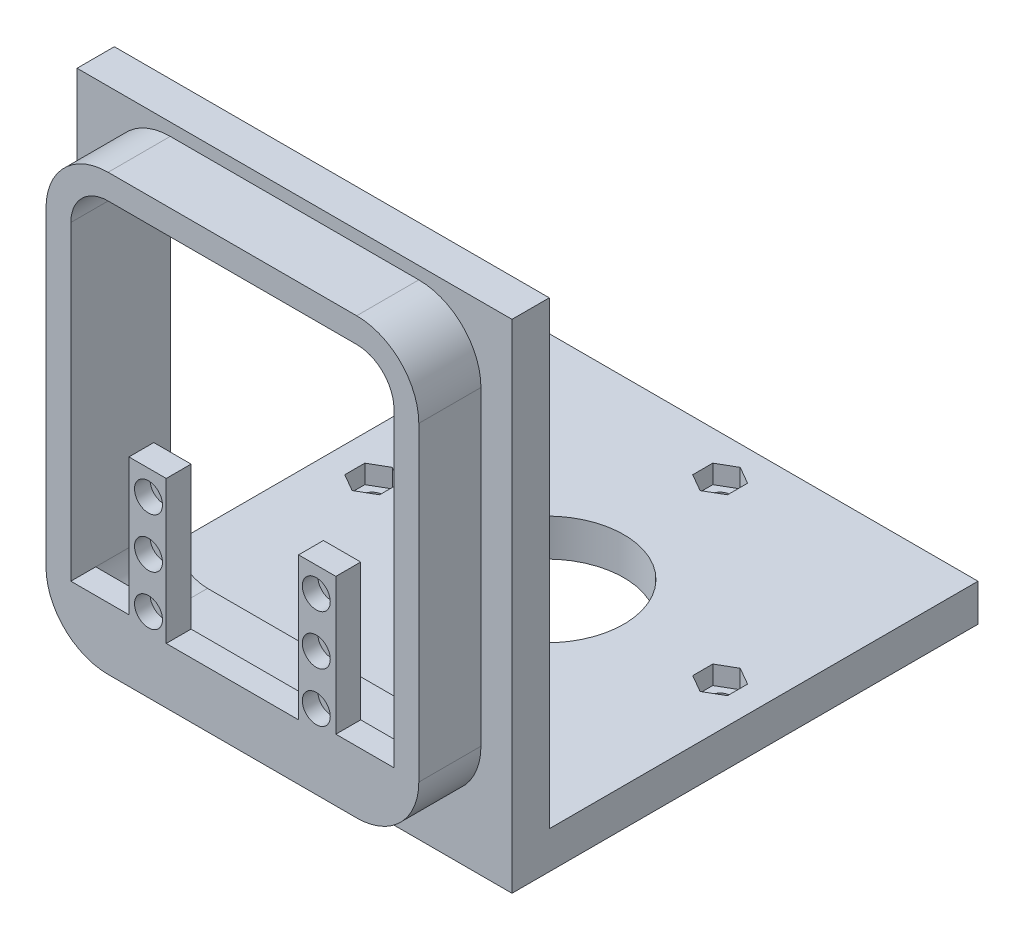
SolidWorks part; units mm, degrees
ref_plane "Front Plane" through (0, 0, 0) normal (0, 0, 1) x (1, 0, 0)
ref_plane "Top Plane" through (0, 0, 0) normal (0, 1, 0) x (1, 0, 0)
ref_plane "Right Plane" through (0, 0, 0) normal (1, 0, 0) x (0, 0, -1)
sketch "Sketch1" plane through (0, 0, 0) normal (0, 0, 1) x (1, 0, 0)
  line L1 (-20, -35) -> (20, -35)
  line L2 (-30, -25) -> (-30, 25)
  line L3 (-20, 35) -> (20, 35)
  line L4 (30, -25) -> (30, 25)
  line L5 (-30, -35) -> (30, 35) construction
  line L6 (-30, 35) -> (30, -35) construction
  arc A1 (20, 35) -> (30, 25) centre (20, 25) cw
  arc A2 (20, -35) -> (30, -25) centre (20, -25) ccw
  arc A3 (-20, -35) -> (-30, -25) centre (-20, -25) cw
  arc A4 (-30, 25) -> (-20, 35) centre (-20, 25) cw
  point P0 (0, 0)
  dimension "D1" = 60
  dimension "D3" = 10
  dimension "D2" = 70
extrude "Boss-Extrude1" add sketch "Sketch1" against normal blind 10
ref_plane "Plane1" through (60, 0, 0) normal (1, 0, 0) x (0, 0, -1)
ref_plane "Plane2" through (60, 0, 0) normal (1, 0, 0) x (0, 0, -1)
sketch "Sketch10" plane through (0, 0, -10) normal (0, 0, -1) x (-1, 0, 0)
  line L0 (0, -3) -> (0, 0) construction
  line L1 (-35, -43) -> (35, -43)
  line L2 (-35, -43) -> (-35, 37)
  line L3 (-35, 37) -> (35, 37)
  line L4 (35, -43) -> (35, 37)
  line L5 (-35, -43) -> (35, 37) construction
  line L6 (-35, 37) -> (35, -43) construction
  point P0 (0, -3)
  dimension "D3" = 3
  dimension "D1" = 80
  dimension "D2" = 70
extrude "Boss-Extrude6" add sketch "Sketch10" along normal blind 75
sketch "Sketch14" plane through (0, 0, 0) normal (0, 0, 1) x (1, 0, 0)
  line L8 (20, 31) -> (-20, 31)
  line L9 (26, -25) -> (26, 25)
  line L10 (-20, -31) -> (20, -31)
  line L11 (-26, 25) -> (-26, -25)
  line L12 (20, 31) -> (-20, 31)
  line L13 (26, -25) -> (26, 25)
  line L14 (-20, -31) -> (20, -31)
  line L15 (-26, 25) -> (-26, -25)
  arc A10 (26, 25) -> (20, 31) centre (20, 25) ccw
  arc A11 (20, -31) -> (26, -25) centre (20, -25) ccw
  arc A12 (-26, -25) -> (-20, -31) centre (-20, -25) ccw
  arc A13 (-20, 31) -> (-26, 25) centre (-20, 25) ccw
  arc A14 (26, 25) -> (20, 31) centre (20, 25) ccw
  arc A15 (20, -31) -> (26, -25) centre (20, -25) ccw
  arc A16 (-26, -25) -> (-20, -31) centre (-20, -25) ccw
  arc A17 (-20, 31) -> (-26, 25) centre (-20, 25) ccw
  dimension "D1" = 4
extrude "Cut-Extrude7" cut sketch "Sketch14" against normal blind 46
sketch "Sketch15" plane through (0, 0, 0) normal (0, 0, 1) x (1, 0, 0)
  line L0 (0, 0) -> (0, -17.9719) construction
  line L1 (-16.65, -3) -> (-10.65, -3)
  line L2 (-10.65, -3) -> (-10.65, -26)
  line L3 (-10.65, -26) -> (10.65, -26)
  line L4 (10.65, -26) -> (10.65, -3)
  line L5 (10.65, -3) -> (16.65, -3)
  line L6 (16.65, -3) -> (16.65, -25)
  line L8 (-16.65, -3) -> (-16.65, -25)
  line L10 (0, 0) -> (13.5, 0) construction
  line L11 (13.5, 0) -> (13.5, -7) construction
  line L12 (13.5, -7) -> (13.5, -15) construction
  line L13 (13.5, -15) -> (13.5, -23) construction
  line L14 (-20, -31) -> (20, -31) construction
  line L15 (-20, -31) -> (20, -31)
  line L16 (26, -25) -> (16.65, -25)
  line L17 (-26, -25) -> (-16.65, -25)
  circle A0 centre (0, 0) radius 11 construction
  circle A1 centre (13.5, -7) radius 1.25
  circle A3 centre (13.5, -15) radius 1.25
  circle A4 centre (13.5, -23) radius 1.25
  circle A5 centre (-13.5, -7) radius 1.25
  circle A6 centre (-13.5, -15) radius 1.25
  circle A7 centre (-13.5, -23) radius 1.25
  arc A9 (-26, -25) -> (-20, -31) centre (-20, -25) ccw
  arc A10 (26, -25) -> (20, -31) centre (20, -25) cw
  point P5 (0, -26)
  dimension "D1" = 22
  dimension "D5" = 2.5
  dimension "D2" = 21.3
  dimension "D3" = 13.5
  dimension "D4" = 7
  dimension "D6" = 8
  dimension "D7" = 8
  dimension "D8" = 6
  dimension "D9" = 5
  dimension "D10" = 3
extrude "Boss-Extrude7" add sketch "Sketch15" against normal blind 4
sketch "Sketch17" plane through (0, 0, 0) normal (0, 0, 1) x (1, 0, 0)
  circle A0 centre (-13.5, -7) radius 2.25
  circle A1 centre (-13.5, -15) radius 2.25
  circle A2 centre (-13.5, -23) radius 2.25
  circle A3 centre (13.5, -7) radius 2.25
  circle A4 centre (13.5, -15) radius 2.25
  circle A5 centre (13.5, -23) radius 2.25
  dimension "D1" = 4.5
extrude "Cut-Extrude9" cut sketch "Sketch17" against normal blind 2.5
sketch "Sketch19" plane through (35, 0, 0) normal (1, 0, 0) x (0, 0, -1)
  line L0 (85, -43) -> (10, -43) construction
  line L1 (85, 37) -> (16, 37)
  line L2 (85, 37) -> (85, -37)
  line L3 (85, -37) -> (16, -37)
  line L4 (16, 37) -> (16, -37)
  line L5 (10, 37) -> (10, -43) construction
  dimension "D1" = 6
  dimension "D2" = 6
extrude "Cut-Extrude11" cut sketch "Sketch19" against normal blind 70
sketch "Sketch20" plane through (0, -43, 0) normal (0, -1, 0) x (1, 0, 0)
  line L0 (-35, -16) -> (35, -85) construction
  line L1 (28, -50.5) -> (0, -50.5) construction
  circle A0 centre (28, -50.5) radius 1.65
  circle A1 centre (0, -78.5) radius 1.65
  circle A2 centre (-28, -50.5) radius 1.65
  circle A4 centre (0, -22.5) radius 1.65 [skipped]
  point P6 (0, -50.5)
  point P16 (0, -50.5)
  dimension "D1" = 3.3
  dimension "D3" = 28
  dimension "D2" = 4
extrude "Cut-Extrude12" cut sketch "Sketch20" against normal blind 10
sketch "Sketch21" plane through (0, -37, 0) normal (0, 1, 0) x (1, 0, 0)
  line L0 (-28, 50.5) -> (28, 50.5) construction
  circle A0 centre (0, 50.5) radius 12.5
  dimension "D1" = 25
extrude "Cut-Extrude13" cut sketch "Sketch21" against normal blind 10
fillet "Fillet2" [suppressed] radius 20
sketch "Sketch22" plane through (0, -37, 0) normal (0, 1, 0) x (1, 0, 0)
  line L1 (0, 81.7332) -> (-2.8, 80.1166)
  line L2 (-2.8, 80.1166) -> (-2.8, 76.8834)
  line L3 (-2.8, 76.8834) -> (0, 75.2668)
  line L4 (0, 75.2668) -> (2.8, 76.8834)
  line L5 (2.8, 76.8834) -> (2.8, 80.1166)
  line L6 (2.8, 80.1166) -> (0, 81.7332)
  line L7 (-30.8, 48.8834) -> (-28, 47.2668)
  line L8 (-28, 47.2668) -> (-25.2, 48.8834)
  line L9 (-25.2, 48.8834) -> (-25.2, 52.1166)
  line L10 (-25.2, 52.1166) -> (-28, 53.7332)
  line L11 (-28, 53.7332) -> (-30.8, 52.1166)
  line L12 (-30.8, 52.1166) -> (-30.8, 48.8834)
  line L19 (28, 53.7332) -> (25.2, 52.1166)
  line L20 (25.2, 52.1166) -> (25.2, 48.8834)
  line L21 (25.2, 48.8834) -> (28, 47.2668)
  line L22 (28, 47.2668) -> (30.8, 48.8834)
  line L23 (30.8, 48.8834) -> (30.8, 52.1166)
  line L24 (30.8, 52.1166) -> (28, 53.7332)
  circle A0 centre (0, 78.5) radius 2.8 construction
  circle A1 centre (-28, 50.5) radius 2.8 construction
  circle A3 centre (28, 50.5) radius 2.8 construction
  dimension "D1" = 5.6
extrude "Cut-Extrude14" cut sketch "Sketch22" against normal blind 3
